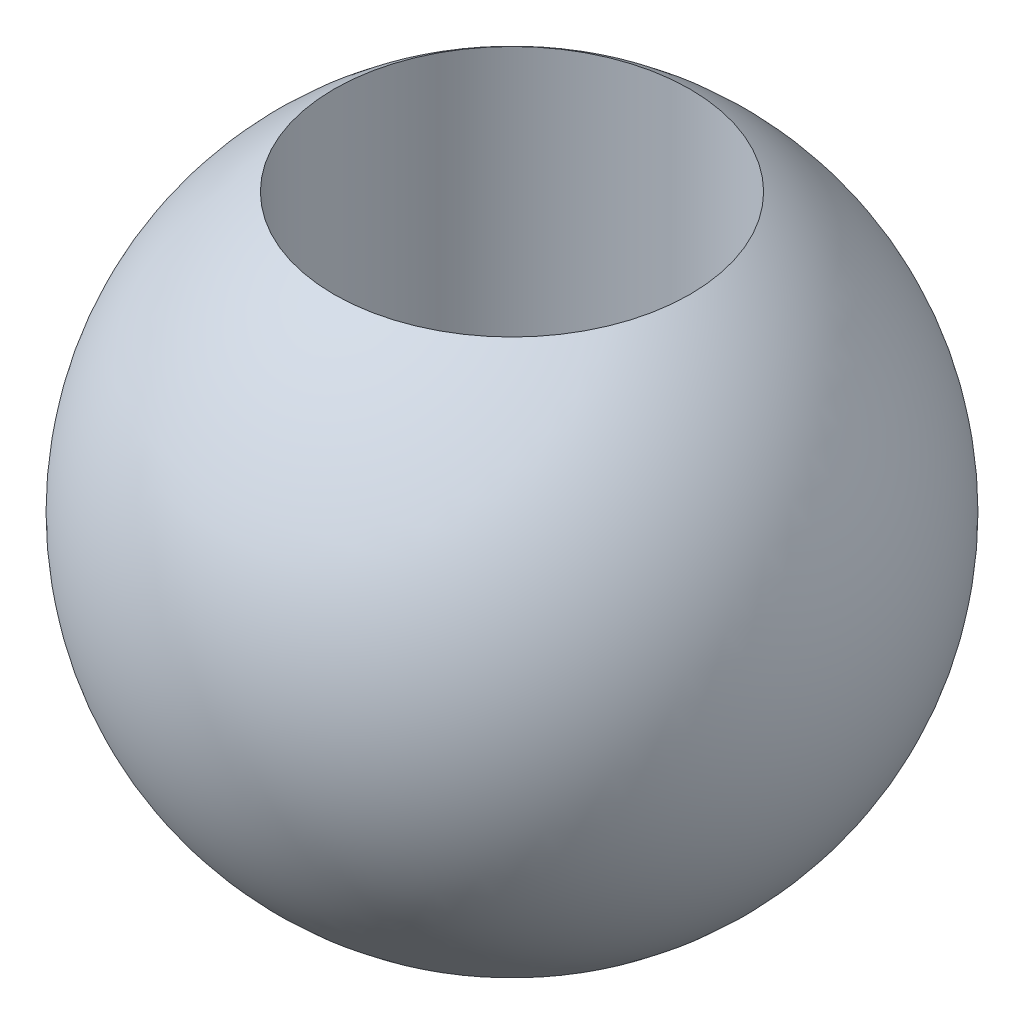
SolidWorks part; units mm, degrees
ref_plane "Front Plane" through (0, 0, 0) normal (0, 0, 1) x (1, 0, 0)
ref_plane "Top Plane" through (0, 0, 0) normal (0, 1, 0) x (1, 0, 0)
ref_plane "Right Plane" through (0, 0, 0) normal (1, 0, 0) x (0, 0, -1)
sketch "Sketch1" plane through (0, 0, 0) normal (0, 0, 1) x (1, 0, 0)
  line L0 (0, 2.54) -> (0, -2.54)
  line L1 (1.3716, 2.803) -> (1.3716, -2.9729)
  arc A0 (0, 2.54) -> (0, -2.54) centre (0, 0) cw
  point P4 (0, 0)
  dimension "D1" = 2.54
  dimension "D2" = 1.3716
revolve "Revolve1" add sketch "Sketch1" angle 360 about L0 region at (1.8496, 0, 0)
